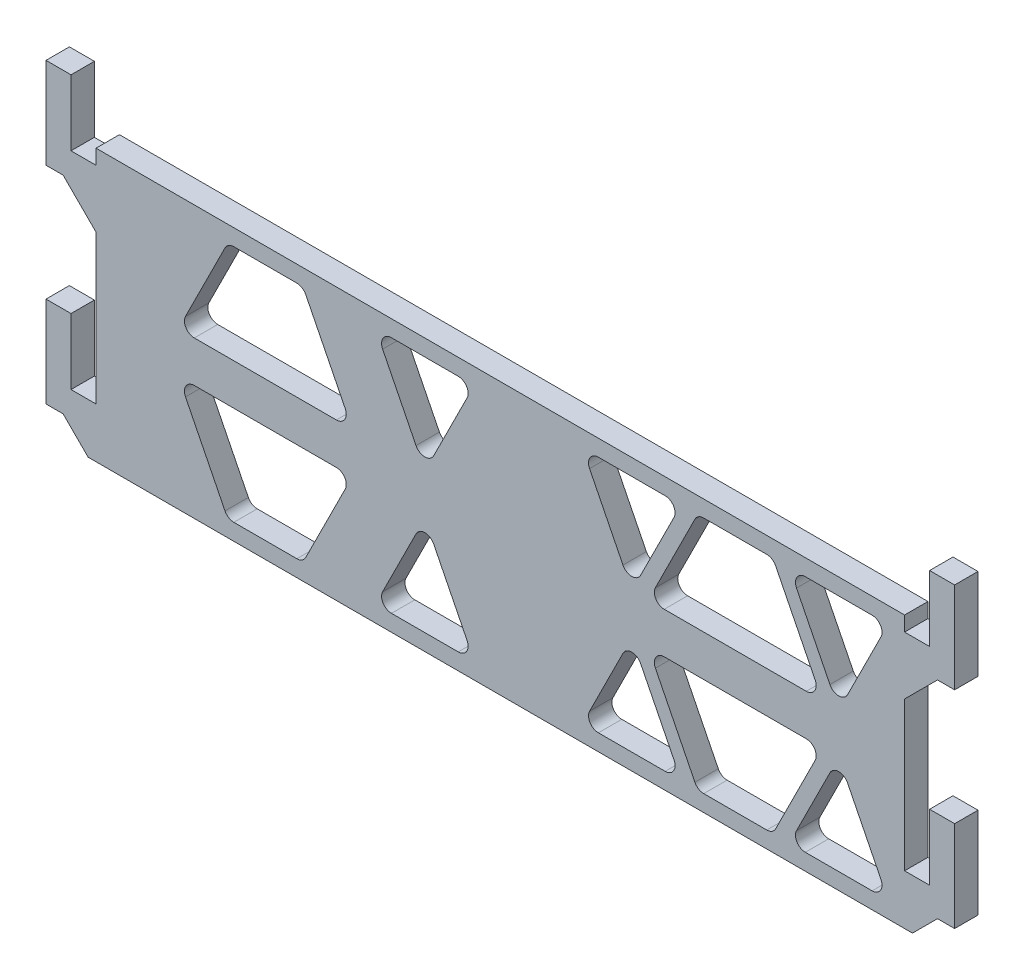
SolidWorks part; units mm, degrees
ref_plane "Front" through (0, 0, 0) normal (0, 0, 1) x (1, 0, 0)
ref_plane "Top" through (0, 0, 0) normal (0, 1, 0) x (1, 0, 0)
ref_plane "Right" through (0, 0, 0) normal (1, 0, 0) x (0, 0, -1)
sketch "Sketch1" plane through (0, 0, 0) normal (0, 0, 1) x (1, 0, 0)
  line L1 (77.978, -34.1605) -> (-77.978, -34.1605)
  line L2 (77.978, -34.1605) -> (77.978, 34.1605)
  line L3 (77.978, 34.1605) -> (-77.978, 34.1605)
  line L4 (-77.978, -34.1605) -> (-77.978, 34.1605)
  line L5 (77.978, -34.1605) -> (-77.978, 34.1605) construction
  line L6 (77.978, 34.1605) -> (-77.978, -34.1605) construction
  point P0 (0, 0)
  dimension "D1" = 155.956
extrude "Boss-Extrude1" add sketch "Sketch1" along normal blind 4.5085
sketch "Sketch2" plane through (0, 0, 4.5085) normal (0, 0, 1) x (1, 0, 0)
  line L0 (77.978, -34.1605) -> (77.978, 34.1605) construction
  line L1 (-77.978, 34.1605) -> (77.978, 34.1605)
  line L2 (-77.978, 34.1605) -> (-77.978, 18.227)
  line L3 (-77.978, 18.227) -> (77.978, 18.227)
  line L4 (77.978, 34.1605) -> (77.978, 18.227)
  dimension "D1" = 15.9335
extrude "Cut-Extrude1" cut sketch "Sketch2" against normal blind 10.795
sketch "Sketch3" plane through (0, 0, 4.5085) normal (0, 0, 1) x (1, 0, 0)
  line L0 (-77.978, 18.227) -> (-77.978, -34.1605) construction
  line L9 (-77.978, 18.227) -> (-77.978, -34.1605) construction
  line L10 (-77.978, -34.1605) -> (77.978, -34.1605) construction
  line L11 (-77.978, -29.3345) -> (-87.63, -29.3345)
  line L12 (-77.978, -29.3345) -> (-77.978, -24.5085)
  line L13 (-77.978, -24.5085) -> (-82.804, -24.5085)
  line L14 (-87.63, -29.3345) -> (-87.63, -25.5891)
  line L16 (-87.63, -25.5891) -> (-87.63, -11.8085)
  line L17 (-87.63, -11.8085) -> (-82.804, -11.8085)
  line L18 (-82.804, -24.5085) -> (-82.804, -11.8085)
  line L19 (-77.978, 10.5435) -> (-87.63, 10.5435)
  line L20 (-77.978, 10.5435) -> (-77.978, 15.3695)
  line L21 (-77.978, 15.3695) -> (-82.804, 15.3695)
  line L24 (-87.63, 28.0695) -> (-82.804, 28.0695)
  line L25 (-82.804, 15.3695) -> (-82.804, 28.0695)
  line L26 (-87.63, 28.0695) -> (-87.63, 10.5435)
  dimension "D1" = 4.826
  dimension "D2" = 4.826
  dimension "D3" = 4.826
  dimension "D4" = 12.7
  dimension "D5" = 22.352
  dimension "D6" = 4.826
  dimension "D7" = 4.826
  dimension "D8" = 4.826
  dimension "D9" = 4.826
  dimension "D10" = 12.7
extrude "Boss-Extrude2" add sketch "Sketch3" against normal blind 4.5085
mirror "Mirror1" about plane through (0, 0, 0) normal (1, 0, 0) of "Boss-Extrude2"
sketch "Sketch4" plane through (0, 0, 0) normal (0, 0, -1) x (-1, 0, 0)
  line L0 (-74.803, 15.052) -> (-55.753, 15.052)
  line L1 (-55.753, 15.052) -> (-65.278, -3.998)
  line L2 (-65.278, -3.998) -> (-74.803, 15.052)
  line L5 (77.978, 18.227) -> (-77.978, 18.227) construction
  dimension "D1" = 19.05
  dimension "D2" = 3.175
  dimension "D3" = 9.525
  dimension "D4" = 19.05
  dimension "D5" = 3.175
extrude "Cut-Extrude2" cut sketch "Sketch4" against normal blind 4.7625
pattern_linear "LPattern1" count 3 spacing 39.9161 along (-1, 0, 0) of "Cut-Extrude2"
sketch "Sketch5" plane through (0, 0, 0) normal (0, 0, -1) x (-1, 0, 0)
  line L0 (-52.578, 15.052) -> (-38.0619, 15.052)
  line L1 (-38.0619, 15.052) -> (-28.5369, -3.998)
  line L2 (-28.5369, -3.998) -> (-62.103, -3.998)
  line L3 (-62.103, -3.998) -> (-52.578, 15.052)
  line L4 (-15.8369, 15.052) -> (-34.8869, 15.052) construction
  dimension "D1" = 3.175
  dimension "D2" = 3.175
  dimension "D3" = 0
  dimension "D4" = 0
  dimension "D5" = 3.175
  dimension "D6" = 3.175
extrude "Cut-Extrude3" cut sketch "Sketch5" against normal blind 4.7625
mirror "Mirror2" about plane through (0, 0, 0) normal (1, 0, 0) of "Cut-Extrude3"
fillet "Fillet2" radius 1.905 9 edges at (-24.0793, 15.052, 2.2542) (-14.5543, -3.998, 2.2542) (-5.0293, 15.052, 2.2542) (15.8369, 15.052, 2.2542) (34.8869, 15.052, 2.2542) (55.753, 15.052, 2.2542) (25.3619, -3.998, 2.2542) (65.278, -3.998, 2.2542) (74.803, 15.052, 2.2542)
ref_plane "Plane1" through (0, -7.9667, 0) normal (0, 1, 0) x (1, 0, 0)
mirror "Mirror3" about plane through (0, -7.9667, 0) normal (0, 1, 0) of "Mirror2", "LPattern1"
fillet "Fillet3" radius 1.905 25 edges at (28.5369, -11.9355, 2.2542) (62.103, -11.9355, 2.2542) (65.278, -11.9355, 2.2542) (55.753, -30.9855, 2.2542) (38.0619, -30.9855, 2.2542) (74.803, -30.9855, 2.2542) (52.578, -30.9855, 2.2542) (34.8869, -30.9855, 2.2542) (25.3619, -11.9355, 2.2542) (15.8369, -30.9855, 2.2542) (-24.0793, -30.9855, 2.2542) (-5.0293, -30.9855, 2.2542) (-14.5543, -11.9355, 2.2542) (-28.5369, -11.9355, 2.2542) (-38.0619, -30.9855, 2.2542) (-52.578, -30.9855, 2.2542) (-62.103, -11.9355, 2.2542) (-62.103, -3.998, 2.2542) (-28.5369, -3.998, 2.2542) (-52.578, 15.052, 2.2542) (-38.0619, 15.052, 2.2542) (52.578, 15.052, 2.2542) (38.0619, 15.052, 2.2542) (28.5369, -3.998, 2.2542) (62.103, -3.998, 2.2542)
chamfer "Chamfer1" distance 6.35 angle 45 4 edges at (-77.978, -29.3345, 2.2542) (-77.978, 10.5435, 2.2542) (77.978, -29.3345, 2.2542) (77.978, 10.5435, 2.2542)
